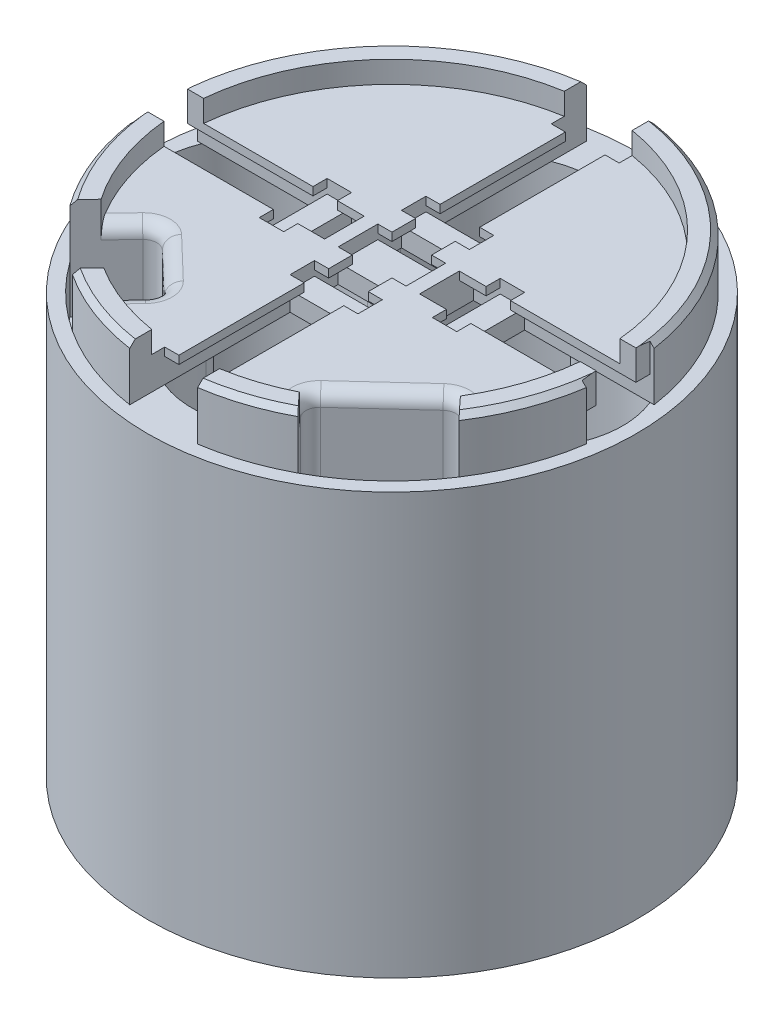
SolidWorks part; units mm, degrees
material "6061 Alloy"
ref_plane "Front Plane" through (0, 0, 0) normal (0, 0, 1) x (1, 0, 0)
ref_plane "Top Plane" through (0, 0, 0) normal (0, 1, 0) x (1, 0, 0)
ref_plane "Right Plane" through (0, 0, 0) normal (1, 0, 0) x (0, 0, -1)
sketch "Sketch1" plane through (0, 0, 0) normal (0, 0, 1) x (1, 0, 0)
  line L0 (0, 0) -> (21.59, 0)
  line L1 (21.59, 0) -> (21.59, -2.54)
  line L2 (21.59, -2.54) -> (22.86, -2.54)
  line L3 (22.86, -2.54) -> (22.86, 36.83)
  line L4 (22.86, 36.83) -> (21.59, 36.83)
  line L5 (21.59, 36.83) -> (21.59, 41.91)
  line L6 (21.59, 41.91) -> (0, 41.91)
  line L7 (0, 41.91) -> (0, 0)
  dimension "D1" = 5.08
  dimension "D2" = 22.86
  dimension "D3" = 1.27
  dimension "D4" = 36.83
  dimension "D5" = 2.54
revolve "Revolve1" add sketch "Sketch1" angle 360 about L7
chamfer "Chamfer1" distance 0.508 angle 45 1 edges at (0, 41.91, 21.59)
sketch "Sketch3" plane through (0, 0, 0) normal (0, 0, 1) x (1, 0, 0)
  line L0 (0, 36.83) -> (3.175, 36.83)
  line L1 (3.175, 36.83) -> (3.175, 39.116)
  line L2 (3.175, 39.116) -> (1.8542, 39.116)
  line L3 (1.8542, 39.116) -> (1.8542, 41.91)
  line L4 (21.082, 41.91) -> (-21.082, 41.91) construction
  line L5 (1.8542, 41.91) -> (-1.8542, 41.91)
  line L6 (-1.8542, 41.91) -> (-1.8542, 39.116)
  line L7 (-1.8542, 39.116) -> (-3.175, 39.116)
  line L8 (-3.175, 39.116) -> (-3.175, 36.83)
  line L9 (-3.175, 36.83) -> (0, 36.83)
  dimension "D1" = 3.7084
  dimension "D2" = 2.794
  dimension "D3" = 2.286
  dimension "D4" = 6.35
extrude "Cut-Extrude1" cut sketch "Sketch3" against normal up to next and the other way up to next
pattern_circular "CirPattern1" count 2 every 90 about axis through (0, 41.91, 0) along (0, 1, 0) of "Cut-Extrude1"
sketch "Sketch4" plane through (0, 0, 0) normal (0, -1, 0) x (1, 0, 0)
  line L0 (-13.208, 0) -> (0, 10.3238) construction
  line L1 (0, 10.3238) -> (13.208, 0) construction
  line L2 (13.208, 0) -> (0, -10.3238) construction
  line L3 (0, -10.3238) -> (-13.208, 0) construction
  line L4 (-18.3636, 0) -> (0, 14.3536) construction
  line L5 (0, 14.3536) -> (18.3636, 0) construction
  line L6 (18.3636, 0) -> (0, -14.3536) construction
  line L7 (0, -14.3536) -> (-18.3636, 0) construction
  line L8 (0, 10.3238) -> (0, 14.3536) construction
  line L9 (0, -14.3536) -> (0, -10.3238) construction
  line L10 (-18.3636, 0) -> (-13.208, 0) construction
  line L11 (13.208, 0) -> (18.3636, 0) construction
  arc A0 (6.604, 5.1619) -> (-6.604, 5.1619) centre (0, 10.3238) ccw
  arc A1 (6.604, -5.1619) -> (6.604, 5.1619) centre (13.208, 0) ccw
  arc A2 (-6.604, -5.1619) -> (6.604, -5.1619) centre (0, -10.3238) ccw
  arc A3 (-6.604, 5.1619) -> (-6.604, -5.1619) centre (-13.208, 0) ccw
  circle A6 centre (0, 0) radius 21.59 construction
  dimension "D1" = 16.764
  dimension "D2" = 3.175
extrude "Cut-Extrude7" cut sketch "Sketch4" against normal up to surface (36.83 mm away) up to face at (-10.2355, 36.83, 10.2355)
sketch "Sketch12" plane through (0, 36.83, 0) normal (0, -1, 0) x (1, 0, 0)
  line L0 (-21.3553, 3.175) -> (-3.175, 3.175) construction
  line L1 (-9.2392, 3.175) -> (-6.9532, 3.175)
  line L2 (-9.2392, 3.175) -> (-9.2392, -3.175)
  line L3 (-9.2392, -3.175) -> (-6.9532, -3.175)
  line L4 (-6.9532, 3.175) -> (-6.9532, -3.175)
  line L5 (-20.9654, -3.175) -> (-3.175, -3.175) construction
  line L6 (-13.208, 8.382) -> (-13.208, 0) construction
  line L7 (-13.208, 0) -> (-9.2392, 0) construction
  line L8 (-3.175, 21.3553) -> (-3.175, 3.175) construction
  line L9 (-3.175, 6.355) -> (3.175, 6.355)
  line L10 (-3.175, 6.355) -> (-3.175, 4.069)
  line L11 (-3.175, 4.069) -> (3.175, 4.069)
  line L12 (3.175, 6.355) -> (3.175, 4.069)
  line L13 (8.382, 10.3238) -> (0, 10.3238) construction
  line L14 (0, 10.3238) -> (0, 6.355) construction
  arc A0 (-6.604, 5.1619) -> (-20.9654, 3.175) centre (-13.208, 0) ccw construction
  arc A1 (6.604, 5.1619) -> (3.175, 18.0812) centre (0, 10.3238) ccw construction
  arc A2 (6.604, 5.1619) -> (-6.604, 5.1619) centre (0, 10.3238) ccw construction
  dimension "D1" = 3.9688
  dimension "D2" = 2.286
extrude "Boss-Extrude2" add sketch "Sketch12" against normal offset from surface (1.778 mm away) 0.508 up to face at (-8.8225, 39.116, 8.8225)
pattern_circular "CirPattern2" count 2 every 180 about axis through (0, 41.91, 0) along (0, 1, 0) of "Boss-Extrude2"
sketch "Sketch15" plane through (0, 36.83, 0) normal (0, -1, 0) x (1, 0, 0)
  line L0 (-3.175, 4.069) -> (-3.175, 3.175) construction
  line L1 (-6.9532, 3.175) -> (-3.175, 3.175) construction
  line L2 (-6.9532, -3.175) -> (-3.175, -3.175) construction
  line L3 (-3.175, 3.175) -> (-4.445, 3.175)
  line L4 (-3.175, 3.175) -> (-3.175, -3.175)
  line L5 (-3.175, -3.175) -> (-4.445, -3.175)
  line L6 (-4.445, 3.175) -> (-4.445, -3.175)
  dimension "D1" = 1.27
extrude "Boss-Extrude3" add sketch "Sketch15" against normal up to surface (5.08 mm away) up to face at (-9.3962, 41.91, 9.3962)
pattern_circular "CirPattern3" count 2 every 180 about axis through (0, 41.91, 0) along (0, 1, 0) of "Boss-Extrude3"
sketch "Sketch16" plane through (0, 41.91, 0) normal (0, 1, 0) x (1, 0, 0)
  line L1 (9.2392, 3.175) -> (6.9532, 3.175)
  line L2 (9.2392, 3.175) -> (9.2392, -3.175)
  line L3 (9.2392, -3.175) -> (6.9532, -3.175)
  line L4 (6.9532, 3.175) -> (6.9532, -3.175)
  line L5 (3.175, -4.069) -> (-3.175, -4.069)
  line L6 (3.175, -4.069) -> (3.175, -6.355)
  line L7 (3.175, -6.355) -> (-3.175, -6.355)
  line L8 (-3.175, -4.069) -> (-3.175, -6.355)
  line L9 (-6.9532, 3.175) -> (-9.2392, 3.175)
  line L10 (-6.9532, 3.175) -> (-6.9532, -3.175)
  line L11 (-6.9532, -3.175) -> (-9.2392, -3.175)
  line L12 (-9.2392, 3.175) -> (-9.2392, -3.175)
  line L13 (3.175, 6.355) -> (-3.175, 6.355)
  line L14 (3.175, 6.355) -> (3.175, 4.069)
  line L15 (3.175, 4.069) -> (-3.175, 4.069)
  line L16 (-3.175, 6.355) -> (-3.175, 4.069)
extrude "Cut-Extrude9" cut sketch "Sketch16" against normal up to next (3.302 mm away)
sketch "Sketch17" plane through (0, 41.91, 0) normal (0, 1, 0) x (1, 0, 0)
  line L0 (3.175, 6.355) -> (3.175, 21.3553) construction
  line L1 (-3.175, 18.0812) -> (3.175, 18.0812)
  line L2 (-3.175, 18.0812) -> (-3.175, 21.59)
  line L3 (-3.175, 21.59) -> (3.175, 21.59)
  line L4 (3.175, 18.0812) -> (3.175, 21.59)
  line L5 (3.175, -18.0812) -> (-3.175, -18.0812)
  line L6 (3.175, -18.0812) -> (3.175, -21.59)
  line L7 (3.175, -21.59) -> (-3.175, -21.59)
  line L8 (-3.175, -18.0812) -> (-3.175, -21.59)
  line L9 (-3.175, -21.3553) -> (-3.175, -6.355) construction
  line L10 (-21.3553, -3.175) -> (-9.2392, -3.175) construction
  line L11 (-20.9654, 3.175) -> (-21.59, 3.175)
  line L12 (-20.9654, 3.175) -> (-20.9654, -3.175)
  line L13 (-20.9654, -3.175) -> (-21.59, -3.175)
  line L14 (-21.59, 3.175) -> (-21.59, -3.175)
  line L15 (21.3553, -3.175) -> (9.2392, -3.175) construction
  line L16 (20.9654, 3.175) -> (21.59, 3.175)
  line L17 (20.9654, 3.175) -> (20.9654, -3.175)
  line L18 (20.9654, -3.175) -> (21.59, -3.175)
  line L19 (21.59, 3.175) -> (21.59, -3.175)
  arc A0 (21.59, 0) -> (-21.59, 0) centre (0, 0) ccw construction
  arc A1 (-21.59, 0) -> (21.59, 0) centre (0, 0) ccw construction
  arc A2 (-1.8542, 21.5102) -> (-21.5102, 1.8542) centre (0, 0) ccw construction
  arc A3 (21.5102, 1.8542) -> (1.8542, 21.5102) centre (0, 0) ccw construction
extrude "Cut-Extrude10" cut sketch "Sketch17" against normal up to surface (5.08 mm away)
fillet "Fillet2" radius 1.27 1 edges at (6.604, 18.415, 5.1619) type face fillet first side face at (0, 24.5533, 12.1139) second side face at (13.6267, 21.0457, 0)
fillet "Fillet3" radius 1.27 1 edges at (6.604, 18.415, -5.1619) type face fillet first side face at (14.6926, 21.0457, 0.1511) second side face at (0, 24.5533, -12.1139)
fillet "Fillet4" radius 1.27 1 edges at (-6.604, 18.415, 5.1619) type face fillet first side face at (-0.2137, 24.5533, 13.0605) second side face at (-13.6267, 21.0457, 0)
fillet "Fillet5" radius 1.27 1 edges at (-6.604, 18.415, -5.1619) type face fillet first side face at (-14.6926, 21.0457, 0.1511) second side face at (-0.2137, 24.5533, -13.0605)
sketch "Sketch18" plane through (0, 36.83, 0) normal (0, -1, 0) x (1, 0, 0)
  line L1 (-3.175, 1.8542) -> (3.175, 1.8542)
  line L2 (-3.175, 1.8542) -> (-3.175, -1.8542)
  line L3 (-3.175, -1.8542) -> (3.175, -1.8542)
  line L4 (3.175, 1.8542) -> (3.175, -1.8542)
extrude "Boss-Extrude4" add sketch "Sketch18" against normal offset from surface (1.778 mm away) 0.508 up to face at (-2.5146, 39.116, -12.2181)
sketch "Sketch19" plane through (0, 41.91, 0) normal (0, 1, 0) x (1, 0, 0)
  line L0 (13.208, 0) -> (14.5679, -9.8524) construction
  line L1 (18.0806, -11.7992) -> (15.5032, -8.9933)
  line L2 (13.7088, -8.9171) -> (7.7227, -14.4154)
  line L3 (7.6465, -16.2098) -> (10.2239, -19.0158)
  line L4 (0, -10.3238) -> (8.5819, -15.3507) construction
  arc A0 (3.175, -21.3553) -> (21.3553, -3.175) centre (0, 0) ccw construction
  arc A1 (18.0806, -11.7992) -> (10.2239, -19.0158) centre (0, 0) cw
  arc A2 (7.7227, -14.4154) -> (7.6465, -16.2098) centre (8.5819, -15.3507) ccw
  arc A3 (15.5032, -8.9933) -> (13.7088, -8.9171) centre (14.5679, -9.8524) ccw
  dimension "D1" = 10.668
  dimension "D3" = 1.27
  dimension "D4" = 21.59
  dimension "D2" = 5.08
extrude "Cut-Extrude11" cut sketch "Sketch19" against normal blind 34.29
sketch "Sketch20" plane through (0, 41.91, 0) normal (0, 1, 0) x (1, 0, 0)
  line L0 (-17.5256, -12.6088) -> (-14.1877, -9.1233)
  line L1 (-12.3921, -9.0844) -> (-8.5397, -12.7736)
  line L2 (-8.5008, -14.5692) -> (-11.8386, -18.0548)
  line L3 (-13.208, 0) -> (-13.2705, -10.0016) construction
  line L4 (0, -10.3238) -> (-9.418, -13.6908) construction
  arc A0 (-21.3553, -3.175) -> (-3.175, -21.3553) centre (0, 0) ccw construction
  arc A1 (-17.5256, -12.6088) -> (-11.8386, -18.0548) centre (0, 0) ccw
  arc A2 (-8.5397, -12.7736) -> (-8.5008, -14.5692) centre (-9.418, -13.6908) cw
  arc A3 (-14.1877, -9.1233) -> (-12.3921, -9.0844) centre (-13.2705, -10.0016) cw
  point P14 (-13.3094, -8.206)
  dimension "D1" = 7.874
  dimension "D3" = 1.27
  dimension "D4" = 21.59
  dimension "D2" = 6.096
extrude "Cut-Extrude12" cut sketch "Sketch20" against normal blind 9.525
chamfer "Chamfer2" distance 0.508 angle 45 1 edges at (0, -2.54, 21.59)
chamfer "Chamfer3" distance 0.508 angle 45 10 edges at (0, 0, 18.7058) (8.7691, 0, 7.9319) (17.8792, 0, 6.9597) (17.8792, 0, -6.9597) (8.7691, 0, -7.9319) (0, 0, -18.7058) (-8.7691, 0, -7.9319) (-17.8792, 0, -6.9597) (-17.8792, 0, 6.9597) (-8.7691, 0, 7.9319)
sketch "Sketch23" plane through (0, 41.91, 0) normal (0, 1, 0) x (1, 0, 0)
  circle A0 centre (0, 0) radius 19.558
  arc A1 (21.3553, 3.175) -> (3.175, 21.3553) centre (0, 0) ccw construction
  dimension "D1" = 2.032
extrude "Cut-Extrude16" cut sketch "Sketch23" against normal blind 2.032
fillet "Fillet8" radius 1.27 1 edges at (-10.4659, 39.878, 10.929) type face fillet first side face at (-6.4622, 39.878, 1.9624) second side face at (10.7158, 23.749, 11.6662) second side face at (-10.4659, 36.1315, 10.929)
fillet "Fillet9" radius 1.27 1 edges at (10.7158, 39.878, 11.6662) type face fillet first side face at (6.4552, 39.878, 2.0407) second side face at (10.7158, 23.749, 11.6662)
